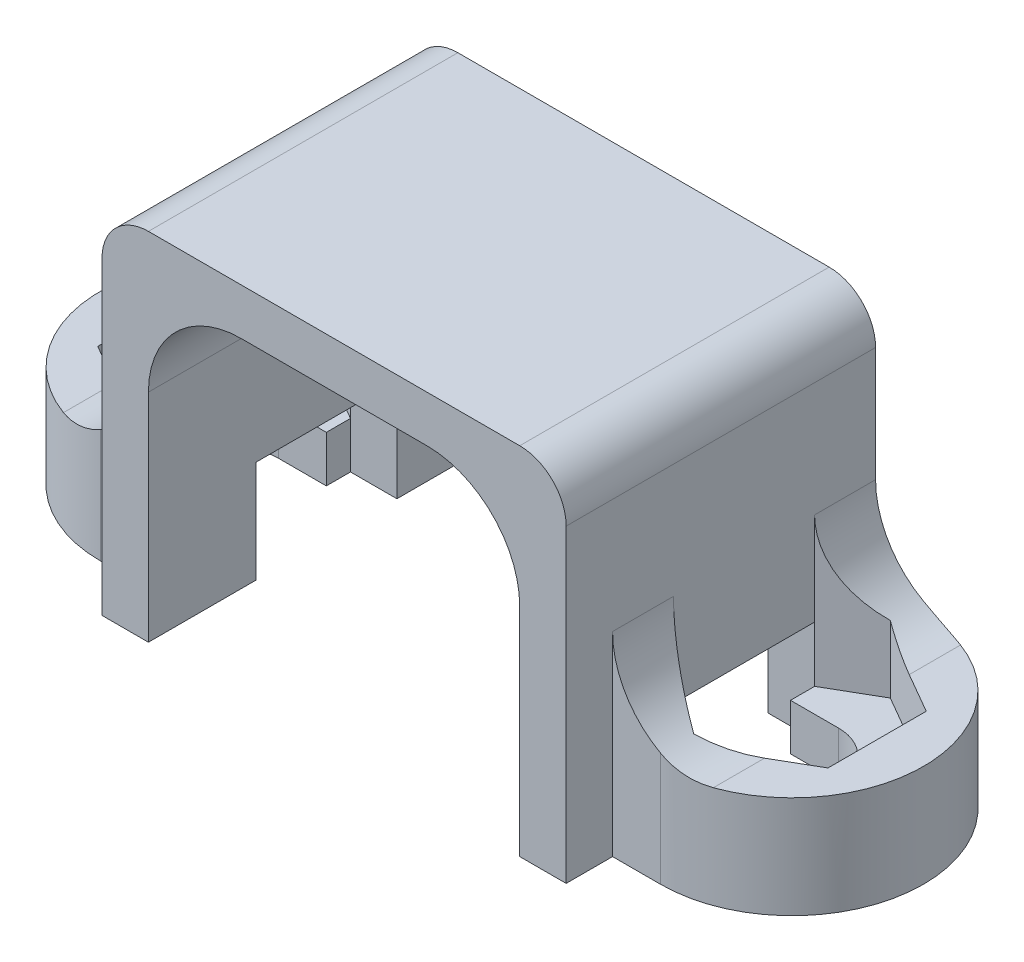
SolidWorks part; units mm, degrees
ref_plane "Front Plane" through (0, 0, 0) normal (0, 0, 1) x (1, 0, 0)
ref_plane "Top Plane" through (0, 0, 0) normal (0, 1, 0) x (1, 0, 0)
ref_plane "Right Plane" through (0, 0, 0) normal (1, 0, 0) x (0, 0, -1)
sketch "Sketch1" plane through (0, 0, 0) normal (0, 0, 1) x (1, 0, 0)
  line L0 (-7.5, 11.5) -> (7.5, 11.5)
  line L3 (-13.3, 0) -> (-6, 0)
  line L4 (-6, 0) -> (-6, 10)
  line L5 (-6, 10) -> (6, 10)
  line L6 (6, 10) -> (6, 0)
  line L7 (6, 0) -> (13.3, 0)
  line L8 (-7.5, 11.5) -> (-7.5, 3.3)
  line L9 (-7.5, 3.3) -> (-13.3, 3.3)
  line L10 (-13.3, 3.3) -> (-13.3, 0)
  line L11 (7.5, 11.5) -> (7.5, 3.3)
  line L12 (7.5, 3.3) -> (13.3, 3.3)
  line L13 (13.3, 3.3) -> (13.3, 0)
  point P4 (0, 10)
  point P19 (0, 11.5)
  dimension "D1" = 11.5
  dimension "D2" = 15
  dimension "D3" = 5.8
  dimension "D4" = 12
  dimension "D5" = 10
  dimension "D6" = 3.3
extrude "Boss-Extrude1" add sketch "Sketch1" along normal mid plane 10
sketch "Sketch2" plane through (0, 3.3, 0) normal (0, 1, 0) x (1, 0, 0)
  line L0 (-13.3, -5) -> (-13.3, 5) construction
  line L1 (13.3, -5) -> (13.3, 5) construction
  line L2 (-7.5, 5) -> (-13.3, 5) construction
  line L3 (-9.05, 5) -> (-13.3, 5)
  line L4 (-13.3, 5) -> (-13.3, 0.75)
  line L5 (-13.3, 0.75) -> (-13.3, -5)
  line L6 (-13.3, -5) -> (-7.5, -5)
  line L7 (-7.5, -5) -> (-7.5, -3.5)
  line L8 (-7.5, -5) -> (-7.5, 5) construction
  line L9 (-7.5, -3.5) -> (-9.05, -3.5)
  line L15 (9.05, -3.5) -> (7.5, -3.5)
  line L16 (7.5, -5) -> (7.5, 5) construction
  line L18 (7.5, -3.5) -> (7.5, -5)
  line L19 (7.5, -5) -> (13.3, -5)
  line L20 (13.3, -5) -> (13.3, 0.75)
  line L21 (13.3, 0.75) -> (13.3, 5)
  line L22 (13.3, 5) -> (9.05, 5)
  arc A0 (-9.05, 5) -> (-9.05, -3.5) centre (-9.05, 0.75) ccw
  arc A1 (9.05, -3.5) -> (9.05, 5) centre (9.05, 0.75) ccw
  line M3 (-7.5, 5) -> (-13.3, 5)
  line M4 (-13.3, 5) -> (-13.3, -5)
  line M5 (-13.3, -5) -> (-7.5, -5)
  line M6 (-7.5, -5) -> (-7.5, 5)
  dimension "D1" = 4.25
extrude "Cut-Extrude1" cut sketch "Sketch2" against normal up to next contours A0 L9 M4 M5 M6 | A0 M3 M4 | A1 L21 L22 | A1 L15 L18 L19 L20 | L21 L22 A1 L15 L18 L19 L20 region at (-12.3507, 3.3, -4.0507) region at (-11.0012, 3.3, 3.7262) region at (11.0012, 3.3, 3.7262) region at (12.3507, 3.3, -4.0507)
sketch "Sketch3" plane through (0, 3.3, 0) normal (0, 1, 0) x (1, 0, 0)
  line L1 (-9.05, 3.9254) -> (-11.8, 2.3377)
  line L2 (-11.8, 2.3377) -> (-11.8, -0.8377)
  line L3 (-11.8, -0.8377) -> (-9.05, -2.4254)
  line L4 (-9.05, -2.4254) -> (-6.3, -0.8377)
  line L5 (-6.3, -0.8377) -> (-6.3, 2.3377)
  line L6 (-6.3, 2.3377) -> (-9.05, 3.9254)
  line L7 (9.05, 3.9254) -> (6.3, 2.3377)
  line L8 (6.3, 2.3377) -> (6.3, -0.8377)
  line L9 (6.3, -0.8377) -> (9.05, -2.4254)
  line L10 (9.05, -2.4254) -> (11.8, -0.8377)
  line L11 (11.8, -0.8377) -> (11.8, 2.3377)
  line L12 (11.8, 2.3377) -> (9.05, 3.9254)
  circle A0 centre (-9.05, 0.75) radius 2.75 construction
  circle A1 centre (9.05, 0.75) radius 2.75 construction
  dimension "D1" = 5.5
extrude "Cut-Extrude2" cut sketch "Sketch3" against normal blind 1.8
fillet "Fillet1" radius 3 6 edges at (6, 10, 0) (-6, 10, 0) (-7.5, 3.3, 2.5153) (7.5, 3.3, -4.0153) (7.5, 3.3, 2.5153) (-7.5, 3.3, -4.0153)
fillet "Fillet2" radius 1.5 2 edges at (7.5, 11.5, 0) (-7.5, 11.5, 0)
sketch "Sketch4" plane through (0, 0, 0) normal (0, 1, 0) x (1, 0, 0)
  line L1 (-11.8, 2.3377) -> (-11.8, -0.8377) construction
  line L2 (-9.05, -0.75) -> (9.05, -0.75)
  line L4 (-9.05, 2.25) -> (9.05, 2.25)
  arc A0 (-9.05, 2.25) -> (-9.05, -0.75) centre (-9.05, 0.75) ccw
  arc A1 (9.05, -0.75) -> (9.05, 2.25) centre (9.05, 0.75) ccw
  point P13 (-11.8, 0.75)
  dimension "D2" = 18.1
  dimension "D3" = 3
extrude "Cut-Extrude3" cut sketch "Sketch4" along normal blind 3
sketch "Sketch5" plane through (0, 0, 0) normal (0, 1, 0) x (1, 0, 0)
  line L1 (7.5, -1.5305) -> (-7.5, -1.5305)
  line L2 (7.5, -1.5305) -> (7.5, 3.0305)
  line L3 (7.5, 3.0305) -> (-7.5, 3.0305)
  line L4 (-7.5, -1.5305) -> (-7.5, 3.0305)
extrude "Cut-Extrude4" cut sketch "Sketch5" along normal up to surface (3.3 mm away) up to face at (6.9, 3.3, -0.75)
